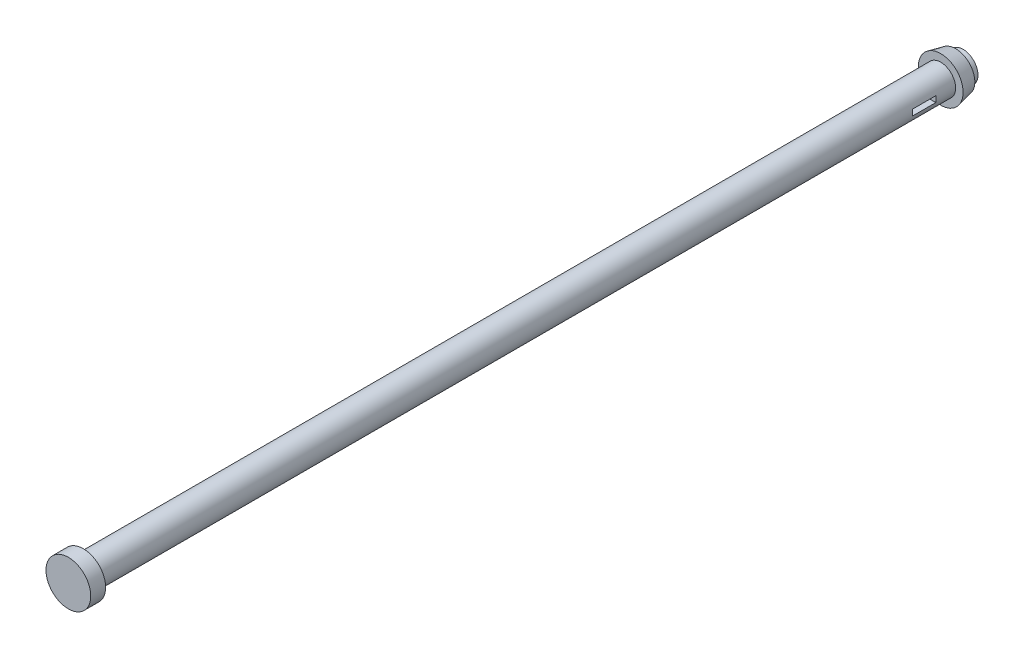
SolidWorks part; units mm, degrees
ref_plane "Front Plane" through (0, 0, 0) normal (0, 0, 1) x (1, 0, 0)
ref_plane "Top Plane" through (0, 0, 0) normal (0, 1, 0) x (1, 0, 0)
ref_plane "Right Plane" through (0, 0, 0) normal (1, 0, 0) x (0, 0, -1)
sketch "Sketch1" plane through (0, 0, 0) normal (0, 1, 0) x (1, 0, 0)
  circle A0 centre (0, 0) radius 10
  dimension "D1" = 20
extrude "Boss-Extrude1" add sketch "Sketch1" along normal blind 590
sketch "Sketch2" plane through (0, 590, 0) normal (0, 1, 0) x (1, 0, 0)
  circle A0 centre (0, 0) radius 15
  dimension "D1" = 30
extrude "Boss-Extrude2" add sketch "Sketch2" along normal blind 10
ref_plane "Plane1" through (0, 15, 0) normal (0, -1, 0) x (-1, 0, 0)
sketch "Sketch3" plane through (0, 15, 0) normal (0, -1, 0) x (-1, 0, 0)
  circle A0 centre (0, 0) radius 15
  dimension "D1" = 30
extrude "Boss-Extrude3" add sketch "Sketch3" along normal blind 10 draft 12
move or copy body "Body-Move/Copy1" bodies to move or copy 103 copy no rotation origin (0, 0, 0) rotation axis (1, 0, 0) rotation angle 90
sketch "Sketch4" plane through (0, 0, 0) normal (0, 1, 0) x (1, 0, 0)
  line L0 (-10, -28.0848) -> (10, -28.0848)
  line L1 (-10, -15) -> (-10, -590) construction
  line L2 (10, -590) -> (10, -15) construction
  line L3 (10, -28.0848) -> (10, -43.8686)
  line L4 (10, -43.8686) -> (-10, -43.8686)
  line L5 (-10, -43.8686) -> (-10, -28.0848)
extrude "Cut-Extrude1" cut sketch "Sketch4" against normal blind 2 and the other way blind 2
